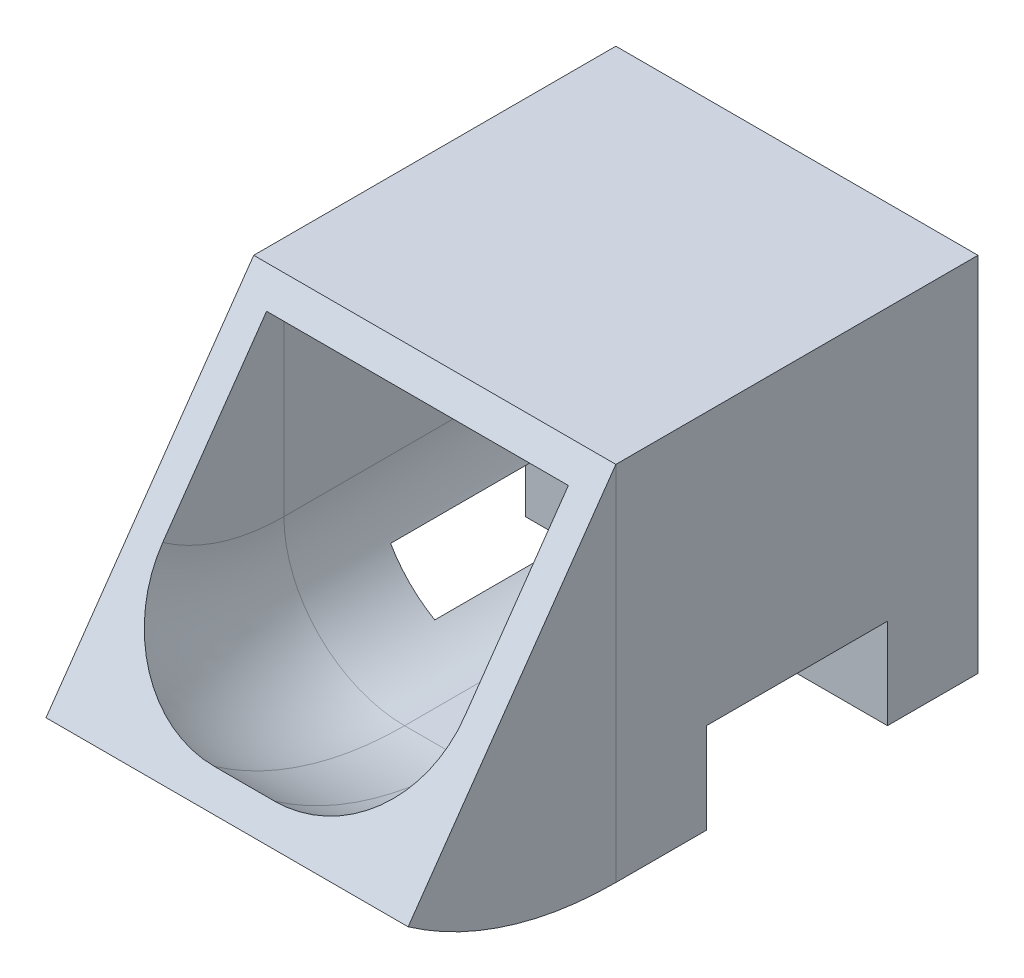
SolidWorks part; units mm, degrees
ref_plane "Plan de face" through (0, 0, 0) normal (0, 0, 1) x (1, 0, 0)
ref_plane "Plan de dessus" through (0, 0, 0) normal (0, 1, 0) x (1, 0, 0)
ref_plane "Plan de droite" through (0, 0, 0) normal (1, 0, 0) x (0, 0, -1)
sketch "Esquisse1" plane through (0, 0, 0) normal (0, 0, 1) x (1, 0, 0)
  line L1 (0, 0) -> (60, 0)
  line L2 (0, 0) -> (0, 60)
  line L3 (0, 60) -> (60, 60)
  line L4 (60, 0) -> (60, 60)
  line L5 (5, 5) -> (55, 5)
  line L6 (5, 5) -> (5, 55)
  line L7 (5, 55) -> (55, 55)
  line L8 (55, 5) -> (55, 55)
  dimension "D3" = 5
  dimension "D5" = 50
  dimension "D1" = 60
  dimension "D2" = 60
  dimension "D4" = 5
  dimension "D6" = 50
extrude "Boss.-Extru.3" add sketch "Esquisse1" along normal blind 60
sketch "Esquisse10" plane through (0, 0, 60) normal (0, 0, 1) x (1, 0, 0)
  line L1 (0, 60) -> (60, 60)
  line L2 (0, 60) -> (0, 0)
  line L3 (0, 0) -> (60, 0)
  line L4 (60, 60) -> (60, 0)
  line L5 (5, 55) -> (55, 55)
  line L6 (5, 55) -> (5, 5)
  line L7 (5, 5) -> (55, 5)
  line L8 (55, 55) -> (55, 5)
revolve "Révolution1" add sketch "Esquisse10" angle 35 about L1 reverse direction yes
sketch "Esquisse11" plane through (0, 0, 0) normal (-1, 0, 0) x (0, 0, 1)
  line L0 (60, 0) -> (0, 0) construction
  line L1 (15, 0) -> (45, 0)
  line L2 (15, 0) -> (15, 15)
  line L3 (15, 15) -> (45, 15)
  line L4 (45, 0) -> (45, 15)
  line L5 (0, 60) -> (0, 0) construction
  point P8 (0, 0)
  dimension "D1" = 30
  dimension "D2" = 15
  dimension "D3" = 15
extrude "Enlèv. mat.-Extru.3" cut sketch "Esquisse11" against normal blind 15
sketch "Esquisse12" plane through (60, 0, 0) normal (1, 0, 0) x (0, 0, -1)
  line L0 (-60, 0) -> (0, 0) construction
  line L1 (-45, 0) -> (-15, 0)
  line L2 (-45, 0) -> (-45, 15)
  line L3 (-45, 15) -> (-15, 15)
  line L4 (-15, 0) -> (-15, 15)
  line L5 (0, 0) -> (0, 60) construction
  dimension "D1" = 30
  dimension "D2" = 15
  dimension "D3" = 15
extrude "Enlèv. mat.-Extru.4" cut sketch "Esquisse12" against normal blind 15
fillet "Congé1" radius 20 1 edges at (55, 5, 52.5)
fillet "Congé3" radius 20 1 edges at (5, 7.5456, 76.5388)
fillet "Congé4" radius 20 1 edges at (55, 7.5456, 76.5388)
fillet "Congé5" radius 20 1 edges at (5, 5, 52.5)
